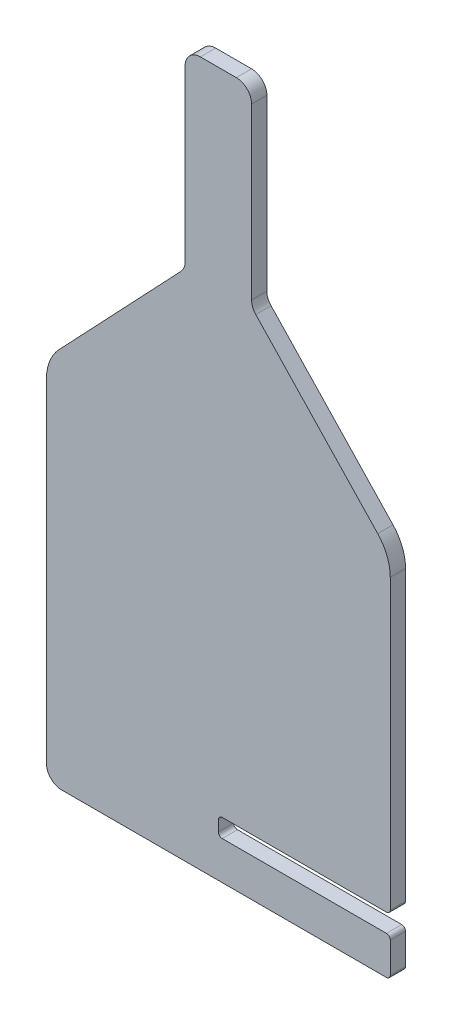
SolidWorks part; units mm, degrees
ref_plane "Alzado" through (0, 0, 0) normal (0, 0, 1) x (1, 0, 0)
ref_plane "Planta" through (0, 0, 0) normal (0, 1, 0) x (1, 0, 0)
ref_plane "Vista lateral" through (0, 0, 0) normal (1, 0, 0) x (0, 0, -1)
sketch "Croquis1" plane through (0, 0, 0) normal (0, 0, 1) x (1, 0, 0)
  line L0 (-4.35, 20) -> (-22.5, 0.8287)
  line L1 (-4.35, 45) -> (4.35, 45)
  line L2 (-22.5, 0.8287) -> (-22.5, -47.1713)
  line L3 (-22.5, -47.1713) -> (22.5, -47.1713)
  line L4 (22.5, 0.8287) -> (22.5, -47.1713)
  line L5 (-4.35, 45) -> (4.35, 45)
  line L6 (-4.35, 45) -> (-4.35, 20)
  line L8 (4.35, 45) -> (4.35, 19.999)
  line L9 (4.35, 19.999) -> (22.5, 0.8287)
  line L10 (0, 72.8664) -> (0, -82.626) construction
  dimension "D1" = 45
  dimension "D2" = 25
  dimension "D3" = 4.35
  dimension "D4" = 22.5
  dimension "D5" = 45
  dimension "D6" = 4.35
  dimension "D7" = 26.3993
  dimension "D8" = 26.4
  dimension "D9" = 48
  dimension "D10" = 48
extrude "Saliente-Extruir1" add sketch "Croquis1" along normal blind 2 contours L6 L0 L2 L3 L4 L9 L8 L1
sketch "Croquis3" plane through (0, 0, 2) normal (0, 0, 1) x (1, 0, 0)
  line L0 (22.5, 0.8287) -> (22.5, -47.1713) construction
  line L1 (22.5, -39.7713) -> (0, -39.7713)
  line L2 (22.5, -39.7713) -> (22.5, -42.1713)
  line L3 (22.5, -42.1713) -> (0, -42.1713)
  line L4 (0, -39.7713) -> (0, -42.1713)
  line L5 (-22.5, -47.1713) -> (22.5, -47.1713) construction
  dimension "D1" = 2.4
  dimension "D2" = 5
  dimension "D3" = 22.5
extrude "Cortar-Extruir2" cut sketch "Croquis3" against normal up to surface (2 mm away) up to face at (0, 4.6642, 0)
fillet "Redondeo1" radius 2 5 edges at (-22.5, -47.1713, 1) (-4.35, 20, 1) (-4.35, 45, 1) (4.35, 19.999, 1) (4.35, 45, 1)
fillet "Redondeo2" radius 6 2 edges at (-22.5, 0.8287, 1) (22.5, 0.8287, 1)
fillet "Redondeo3" radius 0.5 5 edges at (0, -42.1713, 1) (0, -39.7713, 1) (22.5, -42.1713, 1) (22.5, -39.7713, 1) (22.5, -47.1713, 1)
